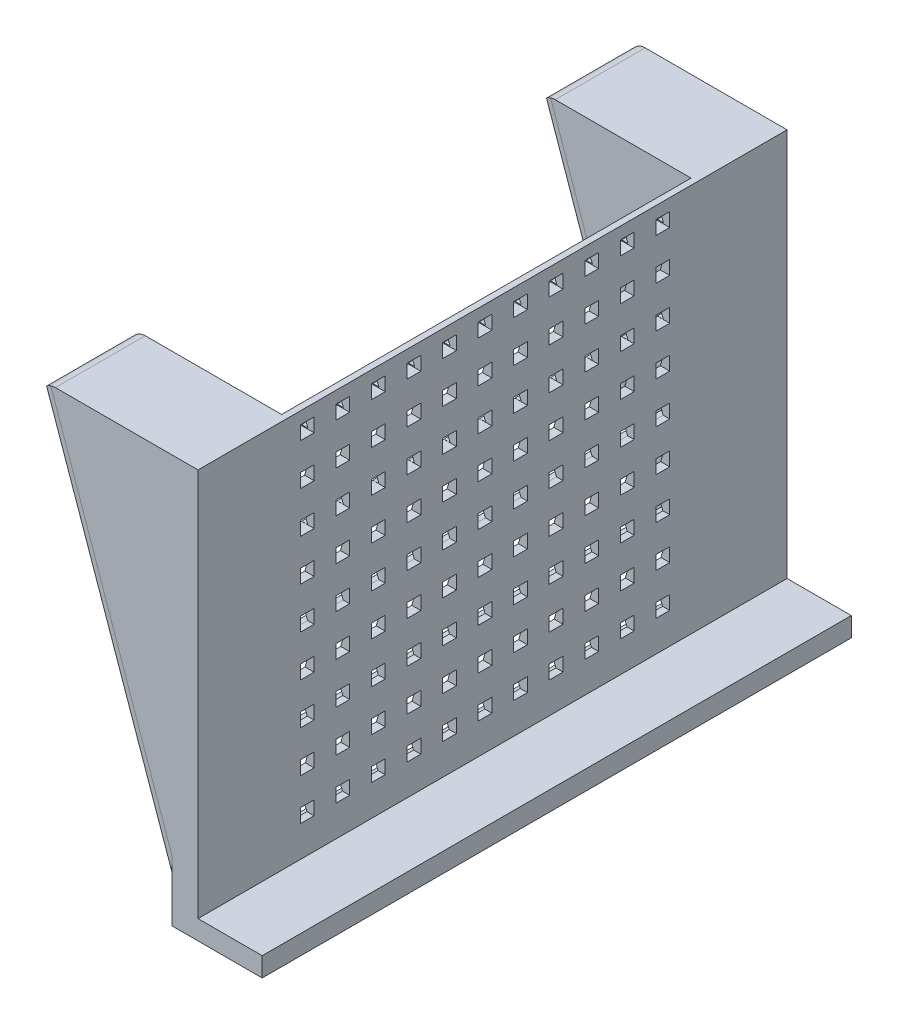
SolidWorks part; units mm, degrees
ref_plane "Front Plane" through (0, 0, 0) normal (0, 0, 1) x (1, 0, 0)
ref_plane "Top Plane" through (0, 0, 0) normal (0, 1, 0) x (1, 0, 0)
ref_plane "Right Plane" through (0, 0, 0) normal (1, 0, 0) x (0, 0, -1)
sketch "Sketch1" plane through (0, 2205.3443, 0) normal (0, -1, 0) x (1, 0, 0)
  line L2 (2715.8216, 1189.2255) -> (2781.2766, 1189.2255)
  line L3 (2715.8216, 1189.2255) -> (2715.8216, 762.9422)
  line L4 (2715.8216, 762.9422) -> (2781.2766, 762.9422)
  line L5 (2781.2766, 1189.2255) -> (2781.2766, 762.9422)
extrude "Boss-Extrude1" add sketch "Sketch1" along normal blind 14
ref_plane "Plane1" through (2725.8216, 0, 0) normal (-1, 0, 0) x (0, 0, 1)
sketch "Sketch2" plane through (2725.8216, 0, 0) normal (-1, 0, 0) x (0, 0, 1)
  line L0 (1189.2255, 2205.3443) -> (762.9422, 2205.3443) construction
  line L1 (827.9422, 2205.3443) -> (1124.2255, 2205.3443)
  line L2 (827.9422, 2205.3443) -> (827.9422, 2486.5313)
  line L3 (827.9422, 2486.5313) -> (1124.2255, 2486.5313)
  line L4 (1124.2255, 2205.3443) -> (1124.2255, 2486.5313)
  line L5 (1268.8186, 2486.5313) -> (684.59, 2486.5313) construction
  line L6 (762.9422, 2191.3443) -> (762.9422, 2205.3443) construction
  line L7 (1189.2255, 2191.3443) -> (1189.2255, 2205.3443) construction
  dimension "D1" = 65
  dimension "D2" = 65
extrude "Boss-Extrude2" add sketch "Sketch2" against normal blind 9
sketch "Sketch3" plane through (0, 0, 1124.2255) normal (0, 0, 1) x (1, 0, 0)
  line L0 (2730.3216, 2486.5313) -> (2727.2973, 2475.891)
  line L1 (2734.8216, 2486.5313) -> (2725.8216, 2486.5313) construction
  line L2 (2725.8216, 2205.3443) -> (2725.8216, 2486.5313) construction
  line L3 (2727.2973, 2475.891) -> (2730.3216, 2468.492)
  line L4 (2730.3216, 2468.492) -> (2725.8216, 2468.492)
  line L5 (2725.8216, 2468.492) -> (2725.8216, 2486.5313)
  line L6 (2725.8216, 2486.5313) -> (2730.3216, 2486.5313)
  line L7 (2730.3216, 2466.3313) -> (2727.2973, 2455.691)
  line L8 (2725.8216, 2466.3313) -> (2730.3216, 2466.3313)
  line L9 (2727.2973, 2455.691) -> (2730.3216, 2448.292)
  line L10 (2730.3216, 2448.292) -> (2725.8216, 2448.292)
  line L11 (2730.3216, 2446.1313) -> (2727.2973, 2435.491)
  line L12 (2725.8216, 2446.1313) -> (2730.3216, 2446.1313)
  line L13 (2727.2973, 2435.491) -> (2730.3216, 2428.092)
  line L14 (2730.3216, 2428.092) -> (2725.8216, 2428.092)
  line L15 (2730.3216, 2425.9313) -> (2727.2973, 2415.291)
  line L16 (2725.8216, 2425.9313) -> (2730.3216, 2425.9313)
  line L17 (2727.2973, 2415.291) -> (2730.3216, 2407.892)
  line L18 (2730.3216, 2407.892) -> (2725.8216, 2407.892)
  line L19 (2730.3216, 2405.7313) -> (2727.2973, 2395.091)
  line L20 (2725.8216, 2405.7313) -> (2730.3216, 2405.7313)
  line L21 (2727.2973, 2395.091) -> (2730.3216, 2387.692)
  line L22 (2730.3216, 2387.692) -> (2725.8216, 2387.692)
  line L23 (2730.3216, 2385.5313) -> (2727.2973, 2374.891)
  line L24 (2725.8216, 2385.5313) -> (2730.3216, 2385.5313)
  line L25 (2727.2973, 2374.891) -> (2730.3216, 2367.492)
  line L26 (2730.3216, 2367.492) -> (2725.8216, 2367.492)
  line L27 (2730.3216, 2365.3313) -> (2727.2973, 2354.691)
  line L28 (2725.8216, 2365.3313) -> (2730.3216, 2365.3313)
  line L29 (2727.2973, 2354.691) -> (2730.3216, 2347.292)
  line L30 (2730.3216, 2347.292) -> (2725.8216, 2347.292)
  line L31 (2730.3216, 2345.1313) -> (2727.2973, 2334.491)
  line L32 (2725.8216, 2345.1313) -> (2730.3216, 2345.1313)
  line L33 (2727.2973, 2334.491) -> (2730.3216, 2327.092)
  line L34 (2730.3216, 2327.092) -> (2725.8216, 2327.092)
  line L35 (2730.3216, 2324.9313) -> (2727.2973, 2314.291)
  line L36 (2725.8216, 2324.9313) -> (2730.3216, 2324.9313)
  line L37 (2727.2973, 2314.291) -> (2730.3216, 2306.892)
  line L38 (2730.3216, 2306.892) -> (2725.8216, 2306.892)
  line L39 (2730.3216, 2304.7313) -> (2727.2973, 2294.091)
  line L40 (2725.8216, 2304.7313) -> (2730.3216, 2304.7313)
  line L41 (2727.2973, 2294.091) -> (2730.3216, 2286.692)
  line L42 (2730.3216, 2286.692) -> (2725.8216, 2286.692)
  line L43 (2730.3216, 2284.5313) -> (2727.2973, 2273.891)
  line L44 (2725.8216, 2284.5313) -> (2730.3216, 2284.5313)
  line L45 (2727.2973, 2273.891) -> (2730.3216, 2266.492)
  line L46 (2730.3216, 2266.492) -> (2725.8216, 2266.492)
  line L47 (2730.3216, 2264.3313) -> (2727.2973, 2253.691)
  line L48 (2725.8216, 2264.3313) -> (2730.3216, 2264.3313)
  line L49 (2727.2973, 2253.691) -> (2730.3216, 2246.292)
  line L50 (2730.3216, 2246.292) -> (2725.8216, 2246.292)
  line L51 (2730.3216, 2244.1313) -> (2727.2973, 2233.491)
  line L52 (2725.8216, 2244.1313) -> (2730.3216, 2244.1313)
  line L53 (2727.2973, 2233.491) -> (2730.3216, 2226.092)
  line L54 (2730.3216, 2226.092) -> (2725.8216, 2226.092)
  line L55 (2730.3216, 2223.9313) -> (2727.2973, 2213.291)
  line L56 (2725.8216, 2223.9313) -> (2730.3216, 2223.9313)
  line L57 (2727.2973, 2213.291) -> (2730.3216, 2205.892)
  line L58 (2730.3216, 2205.892) -> (2725.8216, 2205.892)
  line L59 (2725.8216, 2466.3313) -> (2725.8216, 2205.892)
  line M2 (2725.8216, 2486.5313) -> (2725.8216, 2205.3443)
  line M5 (2734.8216, 2486.5313) -> (2725.8216, 2486.5313)
  dimension "D1" = 14
extrude "Cut-Extrude1" cut sketch "Sketch3" against normal blind 301 contours L22 L21 L19 L20 M2 | L18 L17 L15 L16 M2 | L14 L13 L11 L12 M2 | L10 L9 L7 L8 M2 | L4 L3 L0 M5 M2 | L26 L25 L23 L24 M2 | L30 L29 L27 L28 M2 | L34 L33 L31 L32 M2 | L38 L37 L35 L36 M2 | L42 L41 L39 L40 M2 | L46 L45 L43 L44 M2 | L50 L49 L47 L48 M2 | L54 L53 L51 L52 M2 | L58 L57 L55 L56 M2 region at (2727.4431, 2215.1851, 1124.2255) region at (2727.4431, 2235.3851, 1124.2255) region at (2727.4431, 2255.5851, 1124.2255) region at (2727.4431, 2275.7851, 1124.2255) region at (2727.4431, 2295.9851, 1124.2255) region at (2727.4431, 2316.1851, 1124.2255) region at (2727.4431, 2336.3851, 1124.2255) region at (2727.4431, 2356.5851, 1124.2255) region at (2727.4431, 2376.7851, 1124.2255) region at (2727.4431, 2396.9851, 1124.2255) region at (2727.4431, 2417.1851, 1124.2255) region at (2727.4431, 2437.3851, 1124.2255) region at (2727.4431, 2457.5851, 1124.2255) region at (2727.4431, 2477.7851, 1124.2255)
sketch "Sketch4" plane through (2734.8216, 0, 0) normal (1, 0, 0) x (0, 0, -1)
  line L0 (-1089.4844, 2477.7861) -> (-1089.4844, 2467.7861)
  line L1 (-1115.2183, 2477.7861) -> (-1105.2183, 2477.7861)
  line L2 (-1115.2183, 2477.7861) -> (-1115.2183, 2467.7861)
  line L3 (-1115.2183, 2467.7861) -> (-1105.2183, 2467.7861)
  line L4 (-1105.2183, 2477.7861) -> (-1105.2183, 2467.7861)
  line L5 (-1089.4844, 2477.7861) -> (-1079.4844, 2477.7861)
  line L6 (-1079.4844, 2477.7861) -> (-1079.4844, 2467.7861)
  line L7 (-1089.4844, 2467.7861) -> (-1079.4844, 2467.7861)
  line L8 (-1063.7505, 2477.7861) -> (-1063.7505, 2467.7861)
  line L9 (-1063.7505, 2477.7861) -> (-1053.7505, 2477.7861)
  line L10 (-1053.7505, 2477.7861) -> (-1053.7505, 2467.7861)
  line L11 (-1063.7505, 2467.7861) -> (-1053.7505, 2467.7861)
  line L12 (-1038.0167, 2477.7861) -> (-1038.0167, 2467.7861)
  line L13 (-1038.0167, 2477.7861) -> (-1028.0167, 2477.7861)
  line L14 (-1028.0167, 2477.7861) -> (-1028.0167, 2467.7861)
  line L15 (-1038.0167, 2467.7861) -> (-1028.0167, 2467.7861)
  line L16 (-1012.2828, 2477.7861) -> (-1012.2828, 2467.7861)
  line L17 (-1012.2828, 2477.7861) -> (-1002.2828, 2477.7861)
  line L18 (-1002.2828, 2477.7861) -> (-1002.2828, 2467.7861)
  line L19 (-1012.2828, 2467.7861) -> (-1002.2828, 2467.7861)
  line L20 (-986.5489, 2477.7861) -> (-986.5489, 2467.7861)
  line L21 (-986.5489, 2477.7861) -> (-976.5489, 2477.7861)
  line L22 (-976.5489, 2477.7861) -> (-976.5489, 2467.7861)
  line L23 (-986.5489, 2467.7861) -> (-976.5489, 2467.7861)
  line L24 (-960.8151, 2477.7861) -> (-960.8151, 2467.7861)
  line L25 (-960.8151, 2477.7861) -> (-950.8151, 2477.7861)
  line L26 (-950.8151, 2477.7861) -> (-950.8151, 2467.7861)
  line L27 (-960.8151, 2467.7861) -> (-950.8151, 2467.7861)
  line L28 (-935.0812, 2477.7861) -> (-935.0812, 2467.7861)
  line L29 (-935.0812, 2477.7861) -> (-925.0812, 2477.7861)
  line L30 (-925.0812, 2477.7861) -> (-925.0812, 2467.7861)
  line L31 (-935.0812, 2467.7861) -> (-925.0812, 2467.7861)
  line L32 (-909.3474, 2477.7861) -> (-909.3474, 2467.7861)
  line L33 (-909.3474, 2477.7861) -> (-899.3474, 2477.7861)
  line L34 (-899.3474, 2477.7861) -> (-899.3474, 2467.7861)
  line L35 (-909.3474, 2467.7861) -> (-899.3474, 2467.7861)
  line L36 (-883.6135, 2477.7861) -> (-883.6135, 2467.7861)
  line L37 (-883.6135, 2477.7861) -> (-873.6135, 2477.7861)
  line L38 (-873.6135, 2477.7861) -> (-873.6135, 2467.7861)
  line L39 (-883.6135, 2467.7861) -> (-873.6135, 2467.7861)
  line L40 (-857.8796, 2477.7861) -> (-857.8796, 2467.7861)
  line L41 (-857.8796, 2477.7861) -> (-847.8796, 2477.7861)
  line L42 (-847.8796, 2477.7861) -> (-847.8796, 2467.7861)
  line L43 (-857.8796, 2467.7861) -> (-847.8796, 2467.7861)
  line L44 (-1089.4844, 2447.7861) -> (-1089.4844, 2437.7861)
  line L45 (-1115.2183, 2447.7861) -> (-1105.2183, 2447.7861)
  line L46 (-1115.2183, 2447.7861) -> (-1115.2183, 2437.7861)
  line L47 (-1115.2183, 2437.7861) -> (-1105.2183, 2437.7861)
  line L48 (-1105.2183, 2447.7861) -> (-1105.2183, 2437.7861)
  line L49 (-1089.4844, 2447.7861) -> (-1079.4844, 2447.7861)
  line L50 (-1079.4844, 2447.7861) -> (-1079.4844, 2437.7861)
  line L51 (-1089.4844, 2437.7861) -> (-1079.4844, 2437.7861)
  line L52 (-1063.7505, 2447.7861) -> (-1063.7505, 2437.7861)
  line L53 (-1063.7505, 2447.7861) -> (-1053.7505, 2447.7861)
  line L54 (-1053.7505, 2447.7861) -> (-1053.7505, 2437.7861)
  line L55 (-1063.7505, 2437.7861) -> (-1053.7505, 2437.7861)
  line L56 (-1038.0167, 2447.7861) -> (-1028.0167, 2447.7861)
  line L57 (-1028.0167, 2447.7861) -> (-1028.0167, 2437.7861)
  line L58 (-1038.0167, 2437.7861) -> (-1028.0167, 2437.7861)
  line L59 (-1012.2828, 2447.7861) -> (-1012.2828, 2437.7861)
  line L60 (-1012.2828, 2447.7861) -> (-1002.2828, 2447.7861)
  line L61 (-1002.2828, 2447.7861) -> (-1002.2828, 2437.7861)
  line L62 (-1012.2828, 2437.7861) -> (-1002.2828, 2437.7861)
  line L63 (-986.5489, 2447.7861) -> (-986.5489, 2437.7861)
  line L64 (-986.5489, 2447.7861) -> (-976.5489, 2447.7861)
  line L65 (-976.5489, 2447.7861) -> (-976.5489, 2437.7861)
  line L66 (-986.5489, 2437.7861) -> (-976.5489, 2437.7861)
  line L67 (-960.8151, 2447.7861) -> (-960.8151, 2437.7861)
  line L68 (-960.8151, 2447.7861) -> (-950.8151, 2447.7861)
  line L69 (-950.8151, 2447.7861) -> (-950.8151, 2437.7861)
  line L70 (-960.8151, 2437.7861) -> (-950.8151, 2437.7861)
  line L71 (-935.0812, 2447.7861) -> (-935.0812, 2437.7861)
  line L72 (-935.0812, 2447.7861) -> (-925.0812, 2447.7861)
  line L73 (-925.0812, 2447.7861) -> (-925.0812, 2437.7861)
  line L74 (-935.0812, 2437.7861) -> (-925.0812, 2437.7861)
  line L75 (-909.3474, 2447.7861) -> (-909.3474, 2437.7861)
  line L76 (-909.3474, 2447.7861) -> (-899.3474, 2447.7861)
  line L77 (-899.3474, 2447.7861) -> (-899.3474, 2437.7861)
  line L78 (-909.3474, 2437.7861) -> (-899.3474, 2437.7861)
  line L79 (-883.6135, 2447.7861) -> (-883.6135, 2437.7861)
  line L80 (-883.6135, 2447.7861) -> (-873.6135, 2447.7861)
  line L81 (-873.6135, 2447.7861) -> (-873.6135, 2437.7861)
  line L82 (-883.6135, 2437.7861) -> (-873.6135, 2437.7861)
  line L83 (-857.8796, 2447.7861) -> (-857.8796, 2437.7861)
  line L84 (-857.8796, 2447.7861) -> (-847.8796, 2447.7861)
  line L85 (-847.8796, 2447.7861) -> (-847.8796, 2437.7861)
  line L86 (-857.8796, 2437.7861) -> (-847.8796, 2437.7861)
  line L87 (-1089.4844, 2417.7861) -> (-1089.4844, 2407.7861)
  line L88 (-1115.2183, 2417.7861) -> (-1105.2183, 2417.7861)
  line L89 (-1115.2183, 2417.7861) -> (-1115.2183, 2407.7861)
  line L90 (-1115.2183, 2407.7861) -> (-1105.2183, 2407.7861)
  line L91 (-1105.2183, 2417.7861) -> (-1105.2183, 2407.7861)
  line L92 (-1089.4844, 2417.7861) -> (-1079.4844, 2417.7861)
  line L93 (-1079.4844, 2417.7861) -> (-1079.4844, 2407.7861)
  line L94 (-1089.4844, 2407.7861) -> (-1079.4844, 2407.7861)
  line L95 (-1063.7505, 2417.7861) -> (-1063.7505, 2407.7861)
  line L96 (-1063.7505, 2417.7861) -> (-1053.7505, 2417.7861)
  line L97 (-1053.7505, 2417.7861) -> (-1053.7505, 2407.7861)
  line L98 (-1063.7505, 2407.7861) -> (-1053.7505, 2407.7861)
  line L99 (-1038.0167, 2417.7861) -> (-1028.0167, 2417.7861)
  line L100 (-1028.0167, 2417.7861) -> (-1028.0167, 2407.7861)
  line L101 (-1038.0167, 2407.7861) -> (-1028.0167, 2407.7861)
  line L102 (-1012.2828, 2417.7861) -> (-1012.2828, 2407.7861)
  line L103 (-1012.2828, 2417.7861) -> (-1002.2828, 2417.7861)
  line L104 (-1002.2828, 2417.7861) -> (-1002.2828, 2407.7861)
  line L105 (-1012.2828, 2407.7861) -> (-1002.2828, 2407.7861)
  line L106 (-986.5489, 2417.7861) -> (-986.5489, 2407.7861)
  line L107 (-986.5489, 2417.7861) -> (-976.5489, 2417.7861)
  line L108 (-976.5489, 2417.7861) -> (-976.5489, 2407.7861)
  line L109 (-986.5489, 2407.7861) -> (-976.5489, 2407.7861)
  line L110 (-960.8151, 2417.7861) -> (-960.8151, 2407.7861)
  line L111 (-960.8151, 2417.7861) -> (-950.8151, 2417.7861)
  line L112 (-950.8151, 2417.7861) -> (-950.8151, 2407.7861)
  line L113 (-960.8151, 2407.7861) -> (-950.8151, 2407.7861)
  line L114 (-935.0812, 2417.7861) -> (-935.0812, 2407.7861)
  line L115 (-935.0812, 2417.7861) -> (-925.0812, 2417.7861)
  line L116 (-925.0812, 2417.7861) -> (-925.0812, 2407.7861)
  line L117 (-935.0812, 2407.7861) -> (-925.0812, 2407.7861)
  line L118 (-909.3474, 2417.7861) -> (-909.3474, 2407.7861)
  line L119 (-909.3474, 2417.7861) -> (-899.3474, 2417.7861)
  line L120 (-899.3474, 2417.7861) -> (-899.3474, 2407.7861)
  line L121 (-909.3474, 2407.7861) -> (-899.3474, 2407.7861)
  line L122 (-883.6135, 2417.7861) -> (-883.6135, 2407.7861)
  line L123 (-883.6135, 2417.7861) -> (-873.6135, 2417.7861)
  line L124 (-873.6135, 2417.7861) -> (-873.6135, 2407.7861)
  line L125 (-883.6135, 2407.7861) -> (-873.6135, 2407.7861)
  line L126 (-857.8796, 2417.7861) -> (-857.8796, 2407.7861)
  line L127 (-857.8796, 2417.7861) -> (-847.8796, 2417.7861)
  line L128 (-847.8796, 2417.7861) -> (-847.8796, 2407.7861)
  line L129 (-857.8796, 2407.7861) -> (-847.8796, 2407.7861)
  line L130 (-1089.4844, 2387.7861) -> (-1089.4844, 2377.7861)
  line L131 (-1115.2183, 2387.7861) -> (-1105.2183, 2387.7861)
  line L132 (-1115.2183, 2387.7861) -> (-1115.2183, 2377.7861)
  line L133 (-1115.2183, 2377.7861) -> (-1105.2183, 2377.7861)
  line L134 (-1105.2183, 2387.7861) -> (-1105.2183, 2377.7861)
  line L135 (-1089.4844, 2387.7861) -> (-1079.4844, 2387.7861)
  line L136 (-1079.4844, 2387.7861) -> (-1079.4844, 2377.7861)
  line L137 (-1089.4844, 2377.7861) -> (-1079.4844, 2377.7861)
  line L138 (-1063.7505, 2387.7861) -> (-1063.7505, 2377.7861)
  line L139 (-1063.7505, 2387.7861) -> (-1053.7505, 2387.7861)
  line L140 (-1053.7505, 2387.7861) -> (-1053.7505, 2377.7861)
  line L141 (-1063.7505, 2377.7861) -> (-1053.7505, 2377.7861)
  line L142 (-1038.0167, 2387.7861) -> (-1028.0167, 2387.7861)
  line L143 (-1028.0167, 2387.7861) -> (-1028.0167, 2377.7861)
  line L144 (-1038.0167, 2377.7861) -> (-1028.0167, 2377.7861)
  line L145 (-1012.2828, 2387.7861) -> (-1012.2828, 2377.7861)
  line L146 (-1012.2828, 2387.7861) -> (-1002.2828, 2387.7861)
  line L147 (-1002.2828, 2387.7861) -> (-1002.2828, 2377.7861)
  line L148 (-1012.2828, 2377.7861) -> (-1002.2828, 2377.7861)
  line L149 (-986.5489, 2387.7861) -> (-986.5489, 2377.7861)
  line L150 (-986.5489, 2387.7861) -> (-976.5489, 2387.7861)
  line L151 (-976.5489, 2387.7861) -> (-976.5489, 2377.7861)
  line L152 (-986.5489, 2377.7861) -> (-976.5489, 2377.7861)
  line L153 (-960.8151, 2387.7861) -> (-960.8151, 2377.7861)
  line L154 (-960.8151, 2387.7861) -> (-950.8151, 2387.7861)
  line L155 (-950.8151, 2387.7861) -> (-950.8151, 2377.7861)
  line L156 (-960.8151, 2377.7861) -> (-950.8151, 2377.7861)
  line L157 (-935.0812, 2387.7861) -> (-935.0812, 2377.7861)
  line L158 (-935.0812, 2387.7861) -> (-925.0812, 2387.7861)
  line L159 (-925.0812, 2387.7861) -> (-925.0812, 2377.7861)
  line L160 (-935.0812, 2377.7861) -> (-925.0812, 2377.7861)
  line L161 (-909.3474, 2387.7861) -> (-909.3474, 2377.7861)
  line L162 (-909.3474, 2387.7861) -> (-899.3474, 2387.7861)
  line L163 (-899.3474, 2387.7861) -> (-899.3474, 2377.7861)
  line L164 (-909.3474, 2377.7861) -> (-899.3474, 2377.7861)
  line L165 (-883.6135, 2387.7861) -> (-883.6135, 2377.7861)
  line L166 (-883.6135, 2387.7861) -> (-873.6135, 2387.7861)
  line L167 (-873.6135, 2387.7861) -> (-873.6135, 2377.7861)
  line L168 (-883.6135, 2377.7861) -> (-873.6135, 2377.7861)
  line L169 (-857.8796, 2387.7861) -> (-857.8796, 2377.7861)
  line L170 (-857.8796, 2387.7861) -> (-847.8796, 2387.7861)
  line L171 (-847.8796, 2387.7861) -> (-847.8796, 2377.7861)
  line L172 (-857.8796, 2377.7861) -> (-847.8796, 2377.7861)
  line L173 (-1089.4844, 2357.7861) -> (-1089.4844, 2347.7861)
  line L174 (-1115.2183, 2357.7861) -> (-1105.2183, 2357.7861)
  line L175 (-1115.2183, 2357.7861) -> (-1115.2183, 2347.7861)
  line L176 (-1115.2183, 2347.7861) -> (-1105.2183, 2347.7861)
  line L177 (-1105.2183, 2357.7861) -> (-1105.2183, 2347.7861)
  line L178 (-1089.4844, 2357.7861) -> (-1079.4844, 2357.7861)
  line L179 (-1079.4844, 2357.7861) -> (-1079.4844, 2347.7861)
  line L180 (-1089.4844, 2347.7861) -> (-1079.4844, 2347.7861)
  line L181 (-1063.7505, 2357.7861) -> (-1063.7505, 2347.7861)
  line L182 (-1063.7505, 2357.7861) -> (-1053.7505, 2357.7861)
  line L183 (-1053.7505, 2357.7861) -> (-1053.7505, 2347.7861)
  line L184 (-1063.7505, 2347.7861) -> (-1053.7505, 2347.7861)
  line L185 (-1038.0167, 2357.7861) -> (-1028.0167, 2357.7861)
  line L186 (-1028.0167, 2357.7861) -> (-1028.0167, 2347.7861)
  line L187 (-1038.0167, 2347.7861) -> (-1028.0167, 2347.7861)
  line L188 (-1012.2828, 2357.7861) -> (-1012.2828, 2347.7861)
  line L189 (-1012.2828, 2357.7861) -> (-1002.2828, 2357.7861)
  line L190 (-1002.2828, 2357.7861) -> (-1002.2828, 2347.7861)
  line L191 (-1012.2828, 2347.7861) -> (-1002.2828, 2347.7861)
  line L192 (-986.5489, 2357.7861) -> (-986.5489, 2347.7861)
  line L193 (-986.5489, 2357.7861) -> (-976.5489, 2357.7861)
  line L194 (-976.5489, 2357.7861) -> (-976.5489, 2347.7861)
  line L195 (-986.5489, 2347.7861) -> (-976.5489, 2347.7861)
  line L196 (-960.8151, 2357.7861) -> (-960.8151, 2347.7861)
  line L197 (-960.8151, 2357.7861) -> (-950.8151, 2357.7861)
  line L198 (-950.8151, 2357.7861) -> (-950.8151, 2347.7861)
  line L199 (-960.8151, 2347.7861) -> (-950.8151, 2347.7861)
  line L200 (-935.0812, 2357.7861) -> (-935.0812, 2347.7861)
  line L201 (-935.0812, 2357.7861) -> (-925.0812, 2357.7861)
  line L202 (-925.0812, 2357.7861) -> (-925.0812, 2347.7861)
  line L203 (-935.0812, 2347.7861) -> (-925.0812, 2347.7861)
  line L204 (-909.3474, 2357.7861) -> (-909.3474, 2347.7861)
  line L205 (-909.3474, 2357.7861) -> (-899.3474, 2357.7861)
  line L206 (-899.3474, 2357.7861) -> (-899.3474, 2347.7861)
  line L207 (-909.3474, 2347.7861) -> (-899.3474, 2347.7861)
  line L208 (-883.6135, 2357.7861) -> (-883.6135, 2347.7861)
  line L209 (-883.6135, 2357.7861) -> (-873.6135, 2357.7861)
  line L210 (-873.6135, 2357.7861) -> (-873.6135, 2347.7861)
  line L211 (-883.6135, 2347.7861) -> (-873.6135, 2347.7861)
  line L212 (-857.8796, 2357.7861) -> (-857.8796, 2347.7861)
  line L213 (-857.8796, 2357.7861) -> (-847.8796, 2357.7861)
  line L214 (-847.8796, 2357.7861) -> (-847.8796, 2347.7861)
  line L215 (-857.8796, 2347.7861) -> (-847.8796, 2347.7861)
  line L216 (-1089.4844, 2327.7861) -> (-1089.4844, 2317.7861)
  line L217 (-1115.2183, 2327.7861) -> (-1105.2183, 2327.7861)
  line L218 (-1115.2183, 2327.7861) -> (-1115.2183, 2317.7861)
  line L219 (-1115.2183, 2317.7861) -> (-1105.2183, 2317.7861)
  line L220 (-1105.2183, 2327.7861) -> (-1105.2183, 2317.7861)
  line L221 (-1089.4844, 2327.7861) -> (-1079.4844, 2327.7861)
  line L222 (-1079.4844, 2327.7861) -> (-1079.4844, 2317.7861)
  line L223 (-1089.4844, 2317.7861) -> (-1079.4844, 2317.7861)
  line L224 (-1063.7505, 2327.7861) -> (-1063.7505, 2317.7861)
  line L225 (-1063.7505, 2327.7861) -> (-1053.7505, 2327.7861)
  line L226 (-1053.7505, 2327.7861) -> (-1053.7505, 2317.7861)
  line L227 (-1063.7505, 2317.7861) -> (-1053.7505, 2317.7861)
  line L228 (-1038.0167, 2327.7861) -> (-1028.0167, 2327.7861)
  line L229 (-1028.0167, 2327.7861) -> (-1028.0167, 2317.7861)
  line L230 (-1038.0167, 2317.7861) -> (-1028.0167, 2317.7861)
  line L231 (-1012.2828, 2327.7861) -> (-1012.2828, 2317.7861)
  line L232 (-1012.2828, 2327.7861) -> (-1002.2828, 2327.7861)
  line L233 (-1002.2828, 2327.7861) -> (-1002.2828, 2317.7861)
  line L234 (-1012.2828, 2317.7861) -> (-1002.2828, 2317.7861)
  line L235 (-986.5489, 2327.7861) -> (-986.5489, 2317.7861)
  line L236 (-986.5489, 2327.7861) -> (-976.5489, 2327.7861)
  line L237 (-976.5489, 2327.7861) -> (-976.5489, 2317.7861)
  line L238 (-986.5489, 2317.7861) -> (-976.5489, 2317.7861)
  line L239 (-960.8151, 2327.7861) -> (-960.8151, 2317.7861)
  line L240 (-960.8151, 2327.7861) -> (-950.8151, 2327.7861)
  line L241 (-950.8151, 2327.7861) -> (-950.8151, 2317.7861)
  line L242 (-960.8151, 2317.7861) -> (-950.8151, 2317.7861)
  line L243 (-935.0812, 2327.7861) -> (-935.0812, 2317.7861)
  line L244 (-935.0812, 2327.7861) -> (-925.0812, 2327.7861)
  line L245 (-925.0812, 2327.7861) -> (-925.0812, 2317.7861)
  line L246 (-935.0812, 2317.7861) -> (-925.0812, 2317.7861)
  line L247 (-909.3474, 2327.7861) -> (-909.3474, 2317.7861)
  line L248 (-909.3474, 2327.7861) -> (-899.3474, 2327.7861)
  line L249 (-899.3474, 2327.7861) -> (-899.3474, 2317.7861)
  line L250 (-909.3474, 2317.7861) -> (-899.3474, 2317.7861)
  line L251 (-883.6135, 2327.7861) -> (-883.6135, 2317.7861)
  line L252 (-883.6135, 2327.7861) -> (-873.6135, 2327.7861)
  line L253 (-873.6135, 2327.7861) -> (-873.6135, 2317.7861)
  line L254 (-883.6135, 2317.7861) -> (-873.6135, 2317.7861)
  line L255 (-857.8796, 2327.7861) -> (-857.8796, 2317.7861)
  line L256 (-857.8796, 2327.7861) -> (-847.8796, 2327.7861)
  line L257 (-847.8796, 2327.7861) -> (-847.8796, 2317.7861)
  line L258 (-857.8796, 2317.7861) -> (-847.8796, 2317.7861)
  line L259 (-1089.4844, 2297.7861) -> (-1089.4844, 2287.7861)
  line L260 (-1115.2183, 2297.7861) -> (-1105.2183, 2297.7861)
  line L261 (-1115.2183, 2297.7861) -> (-1115.2183, 2287.7861)
  line L262 (-1115.2183, 2287.7861) -> (-1105.2183, 2287.7861)
  line L263 (-1105.2183, 2297.7861) -> (-1105.2183, 2287.7861)
  line L264 (-1089.4844, 2297.7861) -> (-1079.4844, 2297.7861)
  line L265 (-1079.4844, 2297.7861) -> (-1079.4844, 2287.7861)
  line L266 (-1089.4844, 2287.7861) -> (-1079.4844, 2287.7861)
  line L267 (-1063.7505, 2297.7861) -> (-1063.7505, 2287.7861)
  line L268 (-1063.7505, 2297.7861) -> (-1053.7505, 2297.7861)
  line L269 (-1053.7505, 2297.7861) -> (-1053.7505, 2287.7861)
  line L270 (-1063.7505, 2287.7861) -> (-1053.7505, 2287.7861)
  line L271 (-1038.0167, 2297.7861) -> (-1028.0167, 2297.7861)
  line L272 (-1028.0167, 2297.7861) -> (-1028.0167, 2287.7861)
  line L273 (-1038.0167, 2287.7861) -> (-1028.0167, 2287.7861)
  line L274 (-1012.2828, 2297.7861) -> (-1012.2828, 2287.7861)
  line L275 (-1012.2828, 2297.7861) -> (-1002.2828, 2297.7861)
  line L276 (-1002.2828, 2297.7861) -> (-1002.2828, 2287.7861)
  line L277 (-1012.2828, 2287.7861) -> (-1002.2828, 2287.7861)
  line L278 (-986.5489, 2297.7861) -> (-986.5489, 2287.7861)
  line L279 (-986.5489, 2297.7861) -> (-976.5489, 2297.7861)
  line L280 (-976.5489, 2297.7861) -> (-976.5489, 2287.7861)
  line L281 (-986.5489, 2287.7861) -> (-976.5489, 2287.7861)
  line L282 (-960.8151, 2297.7861) -> (-960.8151, 2287.7861)
  line L283 (-960.8151, 2297.7861) -> (-950.8151, 2297.7861)
  line L284 (-950.8151, 2297.7861) -> (-950.8151, 2287.7861)
  line L285 (-960.8151, 2287.7861) -> (-950.8151, 2287.7861)
  line L286 (-935.0812, 2297.7861) -> (-935.0812, 2287.7861)
  line L287 (-935.0812, 2297.7861) -> (-925.0812, 2297.7861)
  line L288 (-925.0812, 2297.7861) -> (-925.0812, 2287.7861)
  line L289 (-935.0812, 2287.7861) -> (-925.0812, 2287.7861)
  line L290 (-909.3474, 2297.7861) -> (-909.3474, 2287.7861)
  line L291 (-909.3474, 2297.7861) -> (-899.3474, 2297.7861)
  line L292 (-899.3474, 2297.7861) -> (-899.3474, 2287.7861)
  line L293 (-909.3474, 2287.7861) -> (-899.3474, 2287.7861)
  line L294 (-883.6135, 2297.7861) -> (-883.6135, 2287.7861)
  line L295 (-883.6135, 2297.7861) -> (-873.6135, 2297.7861)
  line L296 (-873.6135, 2297.7861) -> (-873.6135, 2287.7861)
  line L297 (-883.6135, 2287.7861) -> (-873.6135, 2287.7861)
  line L298 (-857.8796, 2297.7861) -> (-857.8796, 2287.7861)
  line L299 (-857.8796, 2297.7861) -> (-847.8796, 2297.7861)
  line L300 (-847.8796, 2297.7861) -> (-847.8796, 2287.7861)
  line L301 (-857.8796, 2287.7861) -> (-847.8796, 2287.7861)
  line L302 (-1089.4844, 2267.7861) -> (-1089.4844, 2257.7861)
  line L303 (-1115.2183, 2267.7861) -> (-1105.2183, 2267.7861)
  line L304 (-1115.2183, 2267.7861) -> (-1115.2183, 2257.7861)
  line L305 (-1115.2183, 2257.7861) -> (-1105.2183, 2257.7861)
  line L306 (-1105.2183, 2267.7861) -> (-1105.2183, 2257.7861)
  line L307 (-1089.4844, 2267.7861) -> (-1079.4844, 2267.7861)
  line L308 (-1079.4844, 2267.7861) -> (-1079.4844, 2257.7861)
  line L309 (-1089.4844, 2257.7861) -> (-1079.4844, 2257.7861)
  line L310 (-1063.7505, 2267.7861) -> (-1063.7505, 2257.7861)
  line L311 (-1063.7505, 2267.7861) -> (-1053.7505, 2267.7861)
  line L312 (-1053.7505, 2267.7861) -> (-1053.7505, 2257.7861)
  line L313 (-1063.7505, 2257.7861) -> (-1053.7505, 2257.7861)
  line L314 (-1038.0167, 2267.7861) -> (-1028.0167, 2267.7861)
  line L315 (-1028.0167, 2267.7861) -> (-1028.0167, 2257.7861)
  line L316 (-1038.0167, 2257.7861) -> (-1028.0167, 2257.7861)
  line L317 (-1012.2828, 2267.7861) -> (-1012.2828, 2257.7861)
  line L318 (-1012.2828, 2267.7861) -> (-1002.2828, 2267.7861)
  line L319 (-1002.2828, 2267.7861) -> (-1002.2828, 2257.7861)
  line L320 (-1012.2828, 2257.7861) -> (-1002.2828, 2257.7861)
  line L321 (-986.5489, 2267.7861) -> (-986.5489, 2257.7861)
  line L322 (-986.5489, 2267.7861) -> (-976.5489, 2267.7861)
  line L323 (-976.5489, 2267.7861) -> (-976.5489, 2257.7861)
  line L324 (-986.5489, 2257.7861) -> (-976.5489, 2257.7861)
  line L325 (-960.8151, 2267.7861) -> (-960.8151, 2257.7861)
  line L326 (-960.8151, 2267.7861) -> (-950.8151, 2267.7861)
  line L327 (-950.8151, 2267.7861) -> (-950.8151, 2257.7861)
  line L328 (-960.8151, 2257.7861) -> (-950.8151, 2257.7861)
  line L329 (-935.0812, 2267.7861) -> (-935.0812, 2257.7861)
  line L330 (-935.0812, 2267.7861) -> (-925.0812, 2267.7861)
  line L331 (-925.0812, 2267.7861) -> (-925.0812, 2257.7861)
  line L332 (-935.0812, 2257.7861) -> (-925.0812, 2257.7861)
  line L333 (-909.3474, 2267.7861) -> (-909.3474, 2257.7861)
  line L334 (-909.3474, 2267.7861) -> (-899.3474, 2267.7861)
  line L335 (-899.3474, 2267.7861) -> (-899.3474, 2257.7861)
  line L336 (-909.3474, 2257.7861) -> (-899.3474, 2257.7861)
  line L337 (-883.6135, 2267.7861) -> (-883.6135, 2257.7861)
  line L338 (-883.6135, 2267.7861) -> (-873.6135, 2267.7861)
  line L339 (-873.6135, 2267.7861) -> (-873.6135, 2257.7861)
  line L340 (-883.6135, 2257.7861) -> (-873.6135, 2257.7861)
  line L341 (-857.8796, 2267.7861) -> (-857.8796, 2257.7861)
  line L342 (-857.8796, 2267.7861) -> (-847.8796, 2267.7861)
  line L343 (-847.8796, 2267.7861) -> (-847.8796, 2257.7861)
  line L344 (-857.8796, 2257.7861) -> (-847.8796, 2257.7861)
  line L345 (-1089.4844, 2237.7861) -> (-1089.4844, 2227.7861)
  line L346 (-1115.2183, 2237.7861) -> (-1105.2183, 2237.7861)
  line L347 (-1115.2183, 2237.7861) -> (-1115.2183, 2227.7861)
  line L348 (-1115.2183, 2227.7861) -> (-1105.2183, 2227.7861)
  line L349 (-1105.2183, 2237.7861) -> (-1105.2183, 2227.7861)
  line L350 (-1089.4844, 2237.7861) -> (-1079.4844, 2237.7861)
  line L351 (-1079.4844, 2237.7861) -> (-1079.4844, 2227.7861)
  line L352 (-1089.4844, 2227.7861) -> (-1079.4844, 2227.7861)
  line L353 (-1063.7505, 2237.7861) -> (-1063.7505, 2227.7861)
  line L354 (-1063.7505, 2237.7861) -> (-1053.7505, 2237.7861)
  line L355 (-1053.7505, 2237.7861) -> (-1053.7505, 2227.7861)
  line L356 (-1063.7505, 2227.7861) -> (-1053.7505, 2227.7861)
  line L357 (-1038.0167, 2237.7861) -> (-1028.0167, 2237.7861)
  line L358 (-1028.0167, 2237.7861) -> (-1028.0167, 2227.7861)
  line L359 (-1038.0167, 2227.7861) -> (-1028.0167, 2227.7861)
  line L360 (-1012.2828, 2237.7861) -> (-1012.2828, 2227.7861)
  line L361 (-1012.2828, 2237.7861) -> (-1002.2828, 2237.7861)
  line L362 (-1002.2828, 2237.7861) -> (-1002.2828, 2227.7861)
  line L363 (-1012.2828, 2227.7861) -> (-1002.2828, 2227.7861)
  line L364 (-986.5489, 2237.7861) -> (-986.5489, 2227.7861)
  line L365 (-986.5489, 2237.7861) -> (-976.5489, 2237.7861)
  line L366 (-976.5489, 2237.7861) -> (-976.5489, 2227.7861)
  line L367 (-986.5489, 2227.7861) -> (-976.5489, 2227.7861)
  line L368 (-960.8151, 2237.7861) -> (-960.8151, 2227.7861)
  line L369 (-960.8151, 2237.7861) -> (-950.8151, 2237.7861)
  line L370 (-950.8151, 2237.7861) -> (-950.8151, 2227.7861)
  line L371 (-960.8151, 2227.7861) -> (-950.8151, 2227.7861)
  line L372 (-935.0812, 2237.7861) -> (-935.0812, 2227.7861)
  line L373 (-935.0812, 2237.7861) -> (-925.0812, 2237.7861)
  line L374 (-925.0812, 2237.7861) -> (-925.0812, 2227.7861)
  line L375 (-935.0812, 2227.7861) -> (-925.0812, 2227.7861)
  line L376 (-909.3474, 2237.7861) -> (-909.3474, 2227.7861)
  line L377 (-909.3474, 2237.7861) -> (-899.3474, 2237.7861)
  line L378 (-899.3474, 2237.7861) -> (-899.3474, 2227.7861)
  line L379 (-909.3474, 2227.7861) -> (-899.3474, 2227.7861)
  line L380 (-883.6135, 2237.7861) -> (-883.6135, 2227.7861)
  line L381 (-883.6135, 2237.7861) -> (-873.6135, 2237.7861)
  line L382 (-873.6135, 2237.7861) -> (-873.6135, 2227.7861)
  line L383 (-883.6135, 2227.7861) -> (-873.6135, 2227.7861)
  line L384 (-857.8796, 2237.7861) -> (-857.8796, 2227.7861)
  line L385 (-857.8796, 2237.7861) -> (-847.8796, 2237.7861)
  line L386 (-847.8796, 2237.7861) -> (-847.8796, 2227.7861)
  line L387 (-857.8796, 2227.7861) -> (-847.8796, 2227.7861)
  line L388 (-1038.0167, 2447.7861) -> (-1038.0167, 2437.7861)
  line L389 (-1038.0167, 2417.7861) -> (-1038.0167, 2407.7861)
  line L390 (-1038.0167, 2387.7861) -> (-1038.0167, 2377.7861)
  line L391 (-1038.0167, 2357.7861) -> (-1038.0167, 2347.7861)
  line L392 (-1038.0167, 2327.7861) -> (-1038.0167, 2317.7861)
  line L393 (-1038.0167, 2297.7861) -> (-1038.0167, 2287.7861)
  line L394 (-1038.0167, 2267.7861) -> (-1038.0167, 2257.7861)
  line L395 (-1038.0167, 2237.7861) -> (-1038.0167, 2227.7861)
  dimension "D1" = 11
  dimension "D2" = 9
  dimension "D3" = 10
extrude "Cut-Extrude2" cut sketch "Sketch4" against normal blind 20
sketch "Sketch5" plane through (0, 0, 1124.2255) normal (0, 0, 1) x (1, 0, 0)
  line L0 (2734.8216, 2486.5313) -> (2734.8216, 2205.3443)
  line L1 (2734.8216, 2205.3443) -> (2715.8216, 2205.3443)
  line L2 (2715.8216, 2205.3443) -> (2617.5505, 2486.5313)
  line L3 (2607.2766, 2486.5313) -> (2781.2766, 2486.5313) construction
  line L4 (2617.5505, 2486.5313) -> (2734.8216, 2486.5313)
extrude "Boss-Extrude3" add sketch "Sketch5" along normal up to surface (65 mm away) up to face at (2748.5491, 2198.3443, 1189.2255)
fillet "Fillet1" radius 10 3 edges at (2666.686, 2345.9378, 1189.2255) (2666.686, 2345.9378, 1124.2255) (2617.5505, 2486.5313, 1156.7255)
sketch "Sketch6" plane through (0, 0, 827.9422) normal (0, 0, -1) x (-1, 0, 0)
  line L0 (-2734.8216, 2486.5313) -> (-2617.9991, 2486.5313)
  line L1 (-2607.2766, 2486.5313) -> (-2781.2766, 2486.5313) construction
  line L2 (-2617.9991, 2486.5313) -> (-2715.8216, 2205.3443)
  line L3 (-2715.8216, 2191.3443) -> (-2715.8216, 2205.3443) construction
  line L4 (-2715.8216, 2205.3443) -> (-2781.2766, 2205.3443) construction
  line L5 (-2715.8216, 2205.3443) -> (-2734.8216, 2205.3443)
  line L6 (-2734.8216, 2486.5313) -> (-2734.8216, 2205.3443) construction
  line L7 (-2734.8216, 2205.3443) -> (-2734.8216, 2486.5313)
extrude "Boss-Extrude4" add sketch "Sketch6" along normal up to surface (65 mm away) up to face at (2748.5491, 2198.3443, 762.9422)
fillet "Fillet2" radius 10 3 edges at (2666.9104, 2345.9378, 827.9422) (2666.9104, 2345.9378, 762.9422) (2617.9991, 2486.5313, 795.4422)
